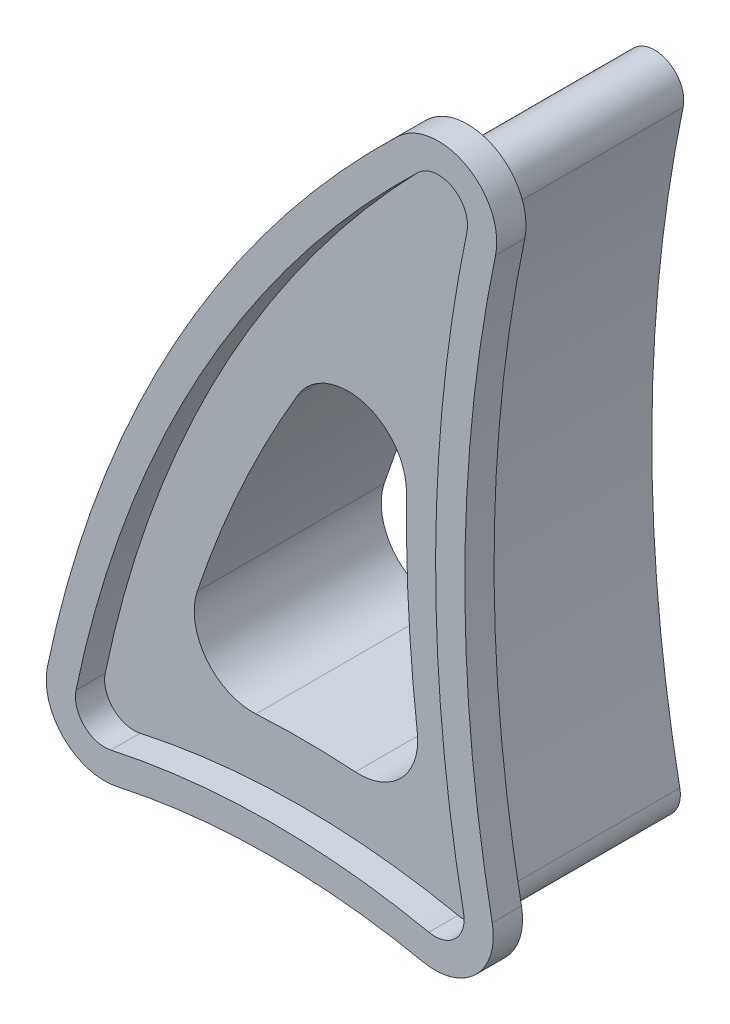
SolidWorks part; units mm, degrees
ref_plane "前视基准面" through (0, 0, 0) normal (0, 0, 1) x (1, 0, 0)
ref_plane "上视基准面" through (0, 0, 0) normal (0, 1, 0) x (1, 0, 0)
ref_plane "右视基准面" through (0, 0, 0) normal (1, 0, 0) x (0, 0, -1)
other "Configuration Table"
sketch "草图1" plane through (0, 0, 0) normal (0, 0, 1) x (1, 0, 0)
  line L0 (-42.4945, 0) -> (51.4094, 0) construction
  line L1 (0, -29.5679) -> (0, 45.0204) construction
  arc A0 (-13.5803, 0.8256) -> (-3.1148, 0.8674) centre (-8.25, -23.5995) cw
  arc A1 (-0.7415, 3.2104) -> (-0.6286, 23.0494) centre (48.3203, 12.851) cw
  arc A2 (-3.9737, 24.8981) -> (-15.9649, 3.1865) centre (25.1569, -5.3576) ccw
  arc A3 (-3.1148, 0.8674) -> (-0.7415, 3.2104) centre (-2.7039, 2.8247) ccw
  arc A4 (-13.5803, 0.8256) -> (-15.9649, 3.1865) centre (-14.0067, 2.7796) cw
  arc A5 (-0.6286, 23.0494) -> (-3.9737, 24.8981) centre (-2.5865, 23.4574) ccw
  arc A6 (-3.2801, 24.1777) -> (-14.9858, 2.9831) centre (25.1569, -5.3576) ccw
  arc A7 (-13.7935, 1.8026) -> (-14.9858, 2.9831) centre (-14.0067, 2.7796) cw
  arc A8 (-13.7935, 1.8026) -> (-2.9094, 1.8461) centre (-8.25, -23.5995) cw
  arc A9 (-2.9094, 1.8461) -> (-1.7227, 3.0175) centre (-2.7039, 2.8247) ccw
  arc A10 (-1.7227, 3.0175) -> (-1.6076, 23.2534) centre (48.3203, 12.851) cw
  arc A11 (-1.6076, 23.2534) -> (-3.2801, 24.1777) centre (-2.5865, 23.4574) ccw
  arc A12 (-8.3965, 14.5212) -> (-11.8383, 6.9858) centre (25.1569, -5.3576) ccw
  arc A14 (-9.8283, 4.356) -> (-6.423, 4.3408) centre (-8.25, -23.5995) cw
  arc A16 (-4.3066, 6.5734) -> (-4.676, 13.4781) centre (48.3203, 12.851) cw
  arc A18 (-3.9469, 4.0678) -> (-4.1417, 20.3832) centre (48.3203, 12.851) cw construction
  arc A19 (-4.1417, 20.3832) -> (-12.6925, 4.0458) centre (25.1569, -5.3576) ccw construction
  arc A20 (-4.676, 13.4781) -> (-8.3965, 14.5212) centre (-6.6759, 13.5018) ccw
  arc A21 (-4.1417, 20.3832) -> (-4.1417, 20.3832) centre (-4.1417, 20.3832) ccw construction
  arc A22 (-12.6925, 4.0458) -> (-3.9469, 4.0678) centre (-8.25, -23.5995) cw construction
  arc A23 (-9.8283, 4.356) -> (-11.8383, 6.9858) centre (-9.9411, 6.3528) cw
  arc A24 (-12.6925, 4.0458) -> (-12.6925, 4.0458) centre (-12.6925, 4.0458) cw construction
  arc A25 (-6.423, 4.3408) -> (-4.3066, 6.5734) centre (-6.2925, 6.3365) ccw
  arc A26 (-3.9469, 4.0678) -> (-3.9469, 4.0678) centre (-3.9469, 4.0678) ccw construction
  point P14 (0, 0)
  point P17 (-16.5, 0)
  point P20 (1, 29)
  dimension "D2" = 50
  dimension "D3" = 25
  dimension "D6" = 42
  dimension "D7" = 2
  dimension "D8" = 2
  dimension "D9" = 2
  dimension "D12" = 2
  dimension "D13" = 2
  dimension "D14" = 2
  dimension "D1" = 16.5
  dimension "D4" = 29
  dimension "D5" = 17.5
  dimension "D10" = 1
  dimension "D11" = 2
extrude "凸台-拉伸1" add sketch "草图1" against normal blind 6.4 contours A10 A11 A6 A7 A8 A9 A25 A14 A23 A12 A20 A16 region at (-2.2303, 24.102, 0)
extrude "凸台-拉伸2" add sketch "草图1<8>" along normal blind 1 separate body contours A1 A5 A2 A4 A0 A3 A11 A10 A9 A8 A7 A6 region at (-15.2091, 1.5652, 0)
sketch "草图1<8>" plane through (0, 0, 0) normal (0, 0, 1) x (1, 0, 0) same geometry as "草图1"
